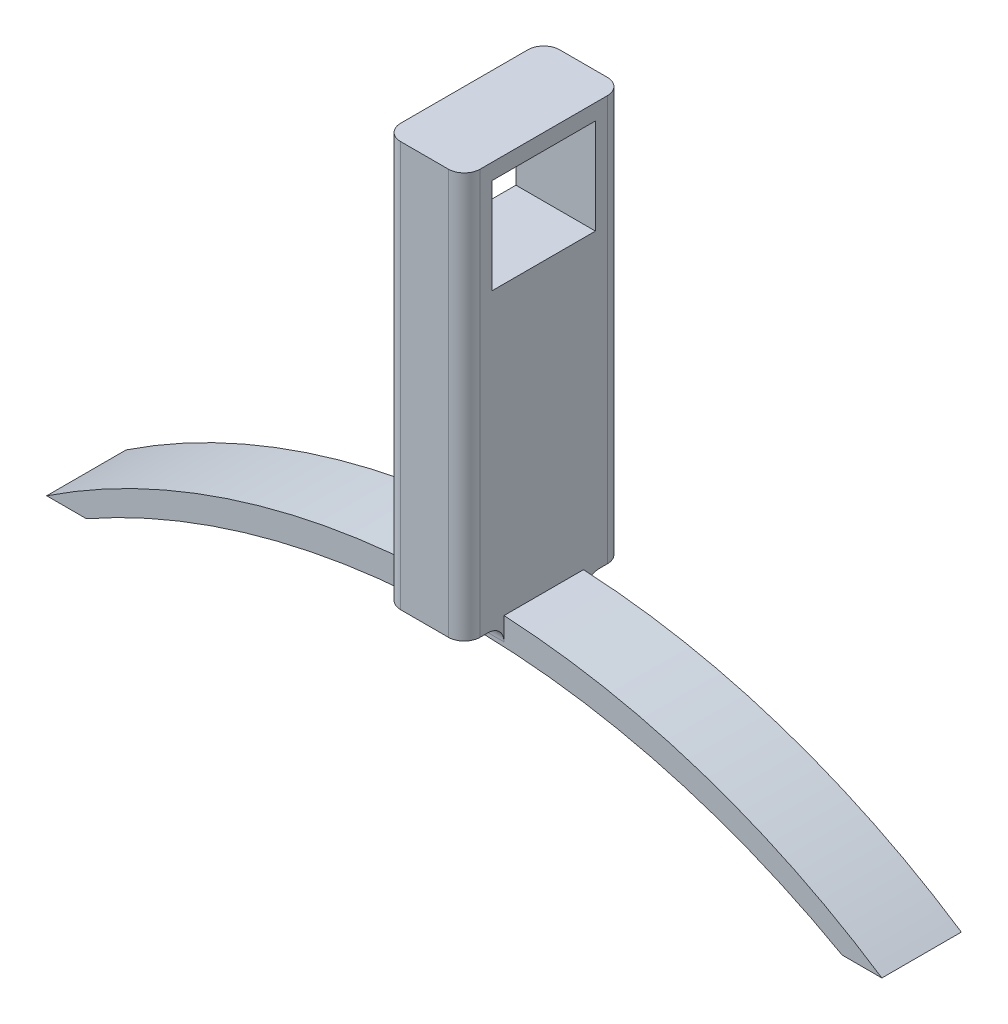
SolidWorks part; units mm, degrees
ref_plane "Front Plane" through (0, 0, 0) normal (0, 0, 1) x (1, 0, 0)
ref_plane "Top Plane" through (0, 0, 0) normal (0, 1, 0) x (1, 0, 0)
ref_plane "Right Plane" through (0, 0, 0) normal (1, 0, 0) x (0, 0, -1)
sketch "Sketch1" plane through (0, 0, 0) normal (0, 0, 1) x (1, 0, 0)
  line L0 (0, 0) -> (5, 0)
  line L1 (105.0571, 0) -> (100.0571, 0)
  arc A0 (0, 0) -> (105.0571, 0) centre (52.5286, -79.1312) cw
  arc A1 (5, 0) -> (100.0571, 0) centre (52.5286, -84.4689) cw
extrude "Boss-Extrude1" add sketch "Sketch1" along normal blind 10
scale "Scale1" scale about centroid uniform scaling yes scale factor 0.5
ref_plane "Plane5" through (0, 12.7861, 0) normal (0, 1, 0) x (1, 0, 0)
sketch "Sketch4" plane through (0, 12.7861, 0) normal (0, 1, 0) x (1, 0, 0)
  line L0 (26.2643, -7.5) -> (78.7928, -7.5) construction
  line L1 (26.2643, -7.5) -> (78.7928, -7.5)
  line L2 (78.7928, -2.5) -> (26.2643, -2.5) construction
  line L3 (78.7928, -2.5) -> (26.2643, -2.5)
  line L4 (52.5286, -2.5) -> (52.5286, -7.5)
  line L6 (50.0286, 0) -> (55.0286, 0)
  line L7 (50.0286, 0) -> (50.0286, -10)
  line L8 (50.0286, -10) -> (55.0286, -10)
  line L9 (55.0286, 0) -> (55.0286, -10)
  line L10 (50.0286, 0) -> (55.0286, -10) construction
  line L11 (50.0286, -10) -> (55.0286, 0) construction
  point P6 (52.5286, -5)
  dimension "D1" = 10
  dimension "D2" = 5
extrude "Boss-Extrude4" add sketch "Sketch4" along normal blind 25 separate body contours L9 L3 L4 L1 | L9 L6 L7 L3 | L3 L7 L1 L4 | L9 L1 L7 L8 region at (51.2786, 12.7861, 5) region at (52.5286, 12.7861, 8.75) region at (53.7786, 12.7861, 5) region at (52.5286, 12.7861, 1.25)
sketch "Sketch5" plane through (0, 12.7861, 0) normal (0, -1, 0) x (1, 0, 0)
  line L4 (50.0286, 0) -> (55.0286, 0)
  line L5 (55.0286, 0) -> (55.0286, 10)
  line L6 (55.0286, 10) -> (50.0286, 10)
  line L7 (50.0286, 10) -> (50.0286, 0)
  line L8 (50.0286, 0) -> (55.0286, 0)
  line L9 (55.0286, 0) -> (55.0286, 10)
  line L10 (55.0286, 10) -> (50.0286, 10)
  line L11 (50.0286, 10) -> (50.0286, 0)
  dimension "D1" = 0
extrude "Boss-Extrude5" add sketch "Sketch5" along normal blind 0.5
fillet "Fillet1" radius 1 6 edges at (52.5286, 12.2861, 2.5) (52.5286, 12.2861, 7.5) (50.0286, 25.0361, 0) (55.0286, 25.0361, 0) (55.0286, 25.0361, 10) (50.0286, 25.0361, 10)
sketch "Sketch6" plane through (55.0286, 0, 0) normal (1, 0, 0) x (0, 0, -1)
  line L0 (-1, 37.7861) -> (-9, 37.7861) construction
  line L1 (-1, 37.7861) -> (-9, 37.7861)
  line L2 (-5, 37.7861) -> (-5, 13.1201) construction
  line L4 (-1.75, 36.7861) -> (-8.25, 36.7861)
  line L5 (-1.75, 36.7861) -> (-1.75, 30.7861)
  line L6 (-1.75, 30.7861) -> (-8.25, 30.7861)
  line L7 (-8.25, 36.7861) -> (-8.25, 30.7861)
  line L8 (-1.75, 36.7861) -> (-8.25, 30.7861) construction
  line L9 (-1.75, 30.7861) -> (-8.25, 36.7861) construction
  point P4 (-5, 33.7861)
  dimension "D1" = 4
  dimension "D2" = 6
  dimension "D3" = 6.5
extrude "Cut-Extrude1" cut sketch "Sketch6" against normal through all contours L4 L7 L6 L5 region at (55.0286, 33.7861, 5)
